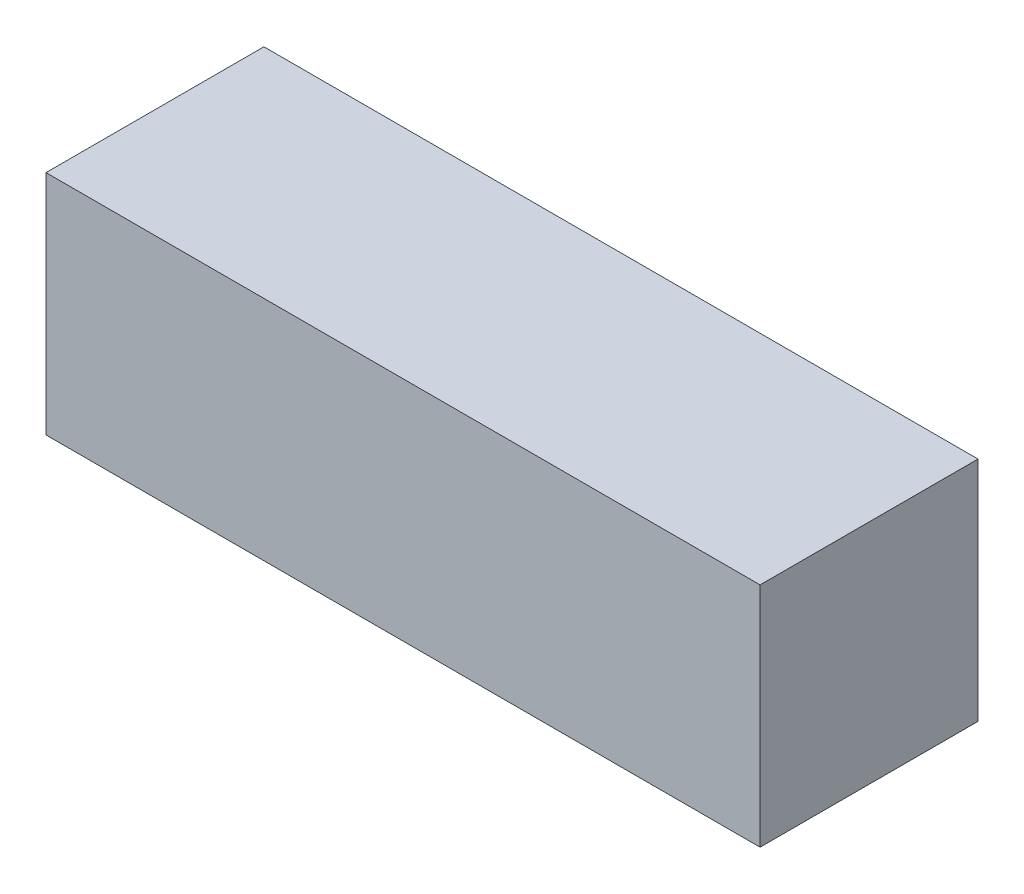
SolidWorks part; units mm, degrees
ref_plane "Front Plane" through (0, 0, 0) normal (0, 0, 1) x (1, 0, 0)
ref_plane "Top Plane" through (0, 0, 0) normal (0, 1, 0) x (1, 0, 0)
ref_plane "Right Plane" through (0, 0, 0) normal (1, 0, 0) x (0, 0, -1)
sketch "Sketch1" plane through (0, 0, 0) normal (0, 1, 0) x (1, 0, 0)
  line L1 (-77, -23.5) -> (77, -23.5)
  line L2 (-77, -23.5) -> (-77, 23.5)
  line L3 (-77, 23.5) -> (77, 23.5)
  line L4 (77, -23.5) -> (77, 23.5)
  line L5 (-77, -23.5) -> (77, 23.5) construction
  line L6 (-77, 23.5) -> (77, -23.5) construction
  point P0 (0, 0)
  dimension "D1" = 154
  dimension "D2" = 47
extrude "Boss-Extrude1" add sketch "Sketch1" along normal blind 49
